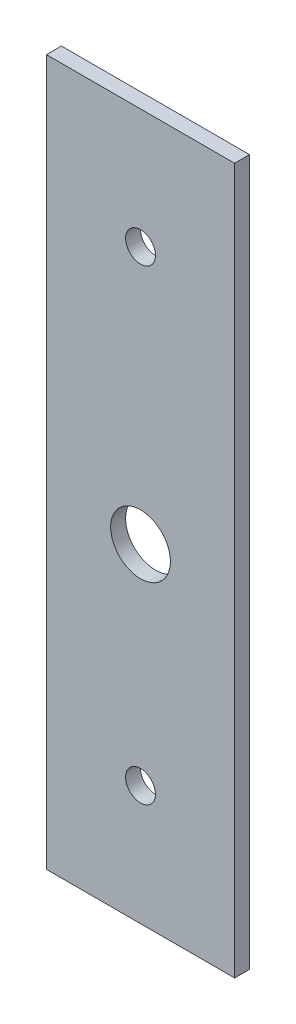
SolidWorks part; units mm, degrees
ref_plane "Front Plane" through (0, 0, 0) normal (0, 0, 1) x (1, 0, 0)
ref_plane "Top Plane" through (0, 0, 0) normal (0, 1, 0) x (1, 0, 0)
ref_plane "Right Plane" through (0, 0, 0) normal (1, 0, 0) x (0, 0, -1)
sketch "Sketch1" plane through (0, 0, 0) normal (0, 0, 1) x (1, 0, 0)
  line L0 (0, 150) -> (0, 0)
  line L1 (0, 0) -> (40, 0)
  line L2 (40, 0) -> (40, 150)
  line L3 (40, 150) -> (0, 150)
  line L4 (20, 150) -> (20, 0) construction
  circle A1 centre (20, 69.85) radius 6.35
  circle A2 centre (20, 25.4) radius 3.175
  circle A4 centre (20, 124.6) radius 3.175
  dimension "D3" = 6.35
  dimension "D4" = 12.7
  dimension "D5" = 6.35
  dimension "D6" = 25.4
  dimension "D1" = 25.4
  dimension "D2" = 40
  dimension "D7" = 44.45
  dimension "D8" = 150
base flange "Base-Flange1" sketch "Sketch1" thickness 3.175 reverse thickness direction no parameters "D1"=0.7366
sketch "Bend-Lines1" [suppressed] plane through (0, 0, 0) normal (0, 1, 0) x (1, 0, 0)
sketch "Bounding-Box1" [suppressed] plane through (0, 0, 0) normal (0, 1, 0) x (1, 0, 0)
sheet metal parameters "Sheet-Metal2" thickness 3.175 parameters "D1"=0.7366
flat pattern "Flat-Pattern2" [suppressed]
sketch "Bend-Lines2" plane through (0, 0, 0) normal (0, 1, 0) x (1, 0, 0)
sketch3d "Bounding-Box2" [suppressed]
  line L0 (40, 150, 0) -> (40, 0, 0) construction
  line L1 (0, 150, 0) -> (0, 0, 0) construction
  line L2 (40, 150, 0) -> (0, 150, 0) construction
  line L3 (40, 0, 0) -> (0, 0, 0) construction
